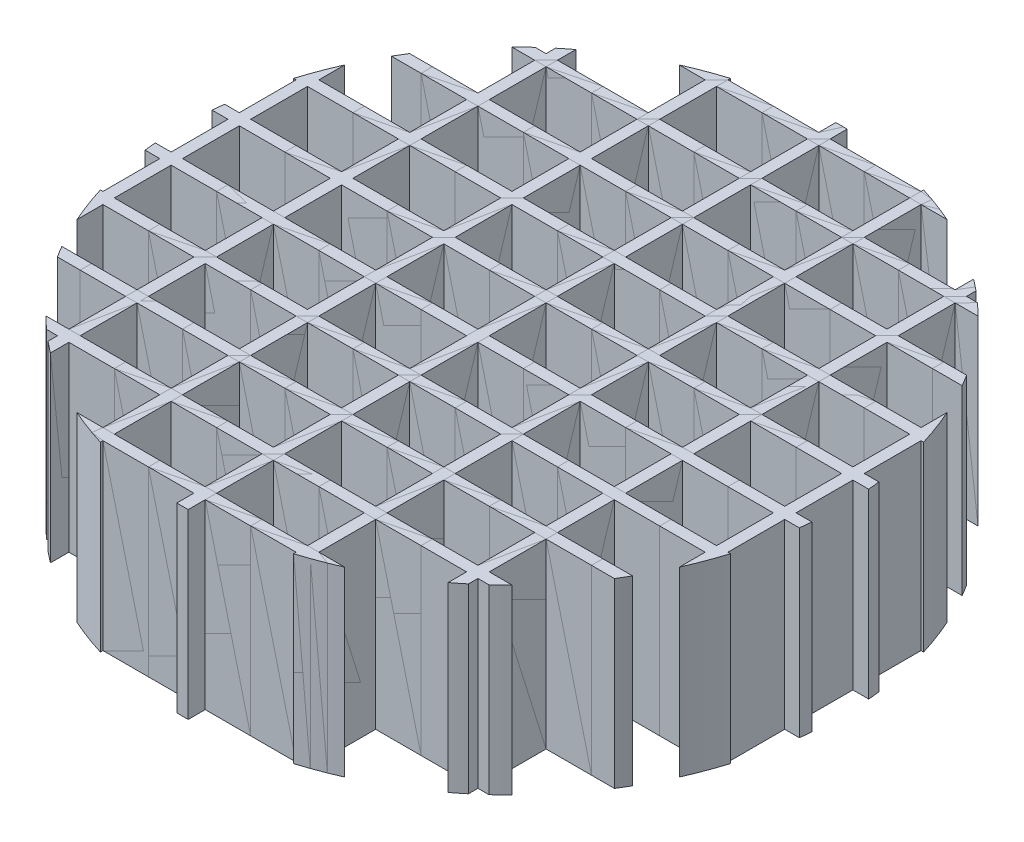
SolidWorks part; units mm, degrees
ref_plane "Front Plane" through (0, 0, 0) normal (0, 0, 1) x (1, 0, 0)
ref_plane "Top Plane" through (0, 0, 0) normal (0, 1, 0) x (1, 0, 0)
ref_plane "Right Plane" through (0, 0, 0) normal (1, 0, 0) x (0, 0, -1)
sketch "Sketch1" plane through (0, 0, 0) normal (0, 1, 0) x (1, 0, 0)
  line L1 (-1.5875, -95.25) -> (1.5875, -95.25)
  line L2 (-1.5875, -95.25) -> (-1.5875, 95.25)
  line L3 (-1.5875, 95.25) -> (1.5875, 95.25)
  line L4 (1.5875, -95.25) -> (1.5875, 95.25)
  line L5 (-1.5875, -95.25) -> (1.5875, 95.25) construction
  line L6 (-1.5875, 95.25) -> (1.5875, -95.25) construction
  point P0 (0, 0)
  dimension "D1" = 190.5
  dimension "D2" = 3.175
extrude "Boss-Extrude1" add sketch "Sketch1" along normal blind 50.8
sketch "Sketch2" plane through (1.5875, 0, 0) normal (1, 0, 0) x (0, 0, -1)
  line L0 (-95.25, 50.8) -> (95.25, 50.8) construction
  line L1 (-87.3125, 50.8) -> (-84.1375, 50.8)
  line L2 (-87.3125, 50.8) -> (-87.3125, 0)
  line L3 (-87.3125, 0) -> (-84.1375, 0)
  line L4 (-84.1375, 50.8) -> (-84.1375, 0)
  line L5 (-95.25, 0) -> (95.25, 0) construction
  line L6 (-95.25, 50.8) -> (-95.25, 0) construction
  dimension "D1" = 3.175
  dimension "D2" = 7.9375
extrude "Boss-Extrude2" add sketch "Sketch2" along normal blind 12.7
pattern_linear "LPattern1" count 10 spacing 19.05 along (0, 0, -1) of "Boss-Extrude2"
pattern_linear "LPattern2" count 2 spacing 15.875 along (-1, 0, 0) of "LPattern1"
pattern_linear "LPattern3" count 4 spacing 28.575 along (1, 0, 0) count 4 spacing 28.575 along (-1, 0, 0) of "Boss-Extrude1", "Boss-Extrude2", "LPattern1", "LPattern2"
sketch "Sketch3" plane through (0, 50.8, 0) normal (0, 1, 0) x (1, 0, 0)
  circle A0 centre (0, 0) radius 92.075
  circle A1 centre (0, 0) radius 152.4
extrude "Cut-Extrude1" cut sketch "Sketch3" against normal through all
